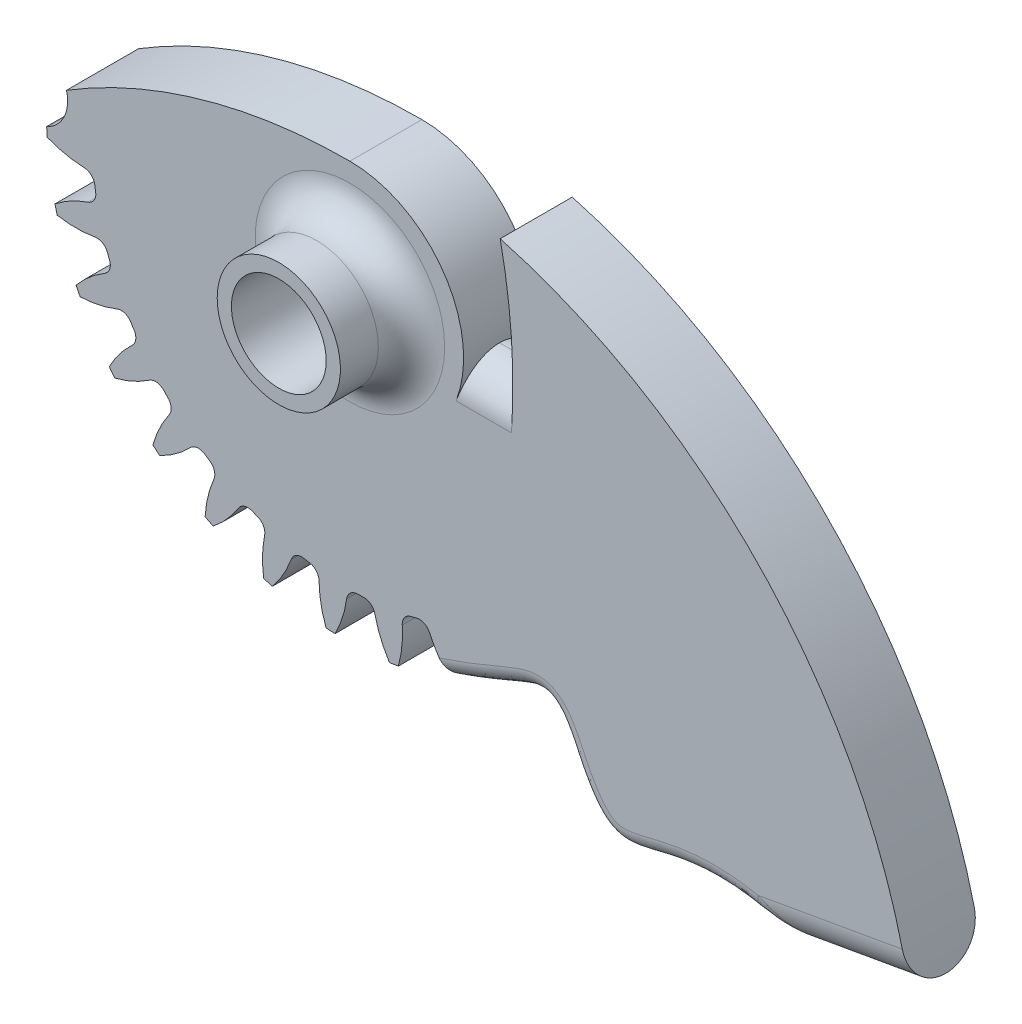
SolidWorks part; units mm, degrees
material "ABS"
ref_plane "Front" through (0, 0, 0) normal (0, 0, 1) x (1, 0, 0)
ref_plane "Top" through (0, 0, 0) normal (0, 1, 0) x (1, 0, 0)
ref_plane "Right" through (0, 0, 0) normal (1, 0, 0) x (0, 0, -1)
sketch "Sketch3" plane through (0, 0, 0) normal (0, 0, 1) x (1, 0, 0)
  circle A0 centre (0, 0) radius 40.64
  dimension "od" = 40.64
extrude "gearBody" add sketch "Sketch3" along normal blind 9.652
sketch "Sketch2" plane through (0, 0, 0) normal (0, 0, 1) x (1, 0, 0)
  line L0 (0, 0) -> (34.0786, 14.1158) construction
  line L1 (45.4751, -11.4855) -> (0, 0) construction
  line L2 (0, 0) -> (36.3143, 0) construction
  line L3 (38.0972, -0.458) -> (37.8451, -4.4001) construction
  line L5 (37.9712, -2.4291) -> (0, 0) construction
  line L7 (0, 0) -> (36.8864, 0) construction
  arc A0 (36.879, -0.7403) -> (36.6727, -3.9649) centre (0, 0) ccw construction
  arc A1 (40.637, 0.4947) -> (40.2427, -5.6687) centre (0, 0) ccw construction
  arc A2 (38.0972, -0.458) -> (37.8451, -4.4001) centre (0, 0) ccw construction
  arc A3 (34.9015, -2.6404) -> (34.9534, -1.8283) centre (0, 0) ccw construction
  arc A4 (45.4751, -11.4855) -> (35.6466, -3.6712) centre (32.0022, -18.3431) ccw construction
  arc A5 (45.4751, -11.4855) -> (46.5679, 5.5974) centre (0, 0) ccw construction
  arc A6 (46.5679, 5.5974) -> (35.8238, -0.9008) centre (34.0786, 14.1158) cw construction
  arc A7 (34.9534, -1.8283) -> (35.8238, -0.9008) centre (35.9376, -1.8798) cw construction
  arc A8 (35.6466, -3.6712) -> (34.9015, -2.6404) centre (35.8842, -2.7147) cw construction
  arc A9 (46.8801, 7.0756) -> (35.7652, -0.3962) centre (34.0786, 14.1158) cw
  arc A10 (34.4461, -1.8018) -> (35.7652, -0.3962) centre (35.9376, -1.8798) cw
  arc A11 (34.3949, -2.6021) -> (34.4461, -1.8018) centre (0, 0) ccw
  arc A12 (35.5241, -4.1642) -> (34.3949, -2.6021) centre (35.8842, -2.7147) cw
  arc A13 (45.5964, -12.9914) -> (35.5241, -4.1642) centre (32.0022, -18.3431) ccw
  arc A14 (45.5964, -12.9914) -> (46.8801, 7.0756) centre (0, 0) ccw
  point P6 (46.5679, 5.5974)
  point P22 (45.4751, -11.4855)
  dimension "D1" = 0.508
  dimension "baseDia" = 73.7729
  dimension "od" = 81.28
  dimension "pd" = 76.2
  dimension "rd" = 70.0024
  dimension "rFillet" = 0.9855
  dimension "pointX" = 46.5679
  dimension "pointY" = 5.5974
  dimension "CTT" = 3.9421
  dimension "flankCenterAngle" = 22.5
extrude "toothCut" cut sketch "Sketch2" along normal through all
pattern_circular "CirPattern1" count 30 over 360 about axis through (0, 0, 9.652) along (0, 0, -1) of "toothCut"
sketch "hub1Dia" plane through (0, 0, 0) normal (0, 0, -1) x (-1, 0, 0)
  circle A0 centre (0, 0) radius 12.7
  dimension "hub1Dia" = 25.4
sketch "hub2Dia" plane through (0, 0, 9.652) normal (0, 0, 1) x (1, 0, 0)
  circle A0 centre (0, 0) radius 12.7
  dimension "hub2dia" = 25.4
sketch "boreDia" plane through (0, 0, 0) normal (0, 0, 1) x (1, 0, 0)
  circle A0 centre (0, 0) radius 6.7469
  dimension "boreDia" = 13.4937
extrude "bore" cut sketch "boreDia" against normal mid plane 25400
sketch "Sketch4" plane through (0, 0, 9.652) normal (0, 0, 1) x (1, 0, 0)
  circle A0 centre (0, -57.15) radius 76.1746
  arc A2 (-41.7195, 6.5842) -> (41.7195, 6.5842) centre (0, 0) cw
  dimension "D1" = 152.3492
  dimension "D2" = 57.15
extrude "Cut-Extrude1" cut sketch "Sketch4" against normal through all contours A0 region at (0, 26.0638, 9.652)
sketch "Sketch5" plane through (0, 0, 9.652) normal (0, 0, 1) x (1, 0, 0)
  line L0 (0, 19.0246) -> (21.5163, 3.7176)
  line L1 (21.5163, 3.7176) -> (10.4433, -33.7781)
  line L2 (10.4433, -33.7781) -> (13.558, -38.3117)
  line L3 (0, 0) -> (0, -57.15) construction
  line L4 (0, -57.15) -> (-54.1615, -3.586) construction
  line L5 (0, -57.15) -> (65.9691, -95.2373) construction
  line L9 (0, -57.15) -> (75.0173, -43.9224) construction
  line L12 (60.232, -46.5295) -> (75.0173, -43.9224)
  line L13 (0, -57.15) -> (29.696, -40.005) construction
  line L14 (29.696, -40.005) -> (26.521, -34.5057) construction
  circle A1 centre (0, -57.15) radius 76.1746 construction
  arc A5 (0, 19.0246) -> (75.0173, -43.9224) centre (0, -57.15) cw
  circle A6 centre (0, -57.15) radius 21.59 construction
  arc A9 (10.6752, -34.1372) -> (8.9309, -33.317) centre (9.3176, -34.7596) ccw construction
  circle A12 centre (49.4934, -85.725) radius 40.64 construction
  spline S0 degree 3 poles (13.558, -38.3117) (21.087, -35.7646) (26.3659, -31.8249) (36.3578, -56.1686) (39.5345, -39.0169) (60.232, -46.5295) knots 0 0 0 0 0.118515 0.218515 1 1 1 1
  point P28 (21.569, -56.1981)
  dimension "D1" = 43.18
  dimension "D3" = 81.28
  dimension "D6" = 152.3492
  dimension "D2" = 120
  dimension "D4" = 57.15
  dimension "D8" = 57.15
  dimension "D7" = 60
  dimension "D9" = 34.29
  dimension "D10" = 6.35
  dimension "D5" = 80
extrude "Boss-Extrude1" add sketch "Sketch5" against normal up to surface (9.652 mm away) up to face at (6.7469, 0, 0)
sketch "Sketch6" plane through (0, 0, 9.652) normal (0, 0, 1) x (1, 0, 0)
  line L1 (-41.2993, 3.0747) -> (-42.3397, 6.1739)
  line L2 (15.875, 0) -> (21.209, 0)
  circle A0 centre (0, -57.15) radius 76.1746 construction
  arc A1 (75.0173, -43.9224) -> (-33.55, 11.2383) centre (0, -57.15) ccw construction
  circle A2 centre (0, 0) radius 15.875 construction
  arc A3 (0, 15.875) -> (15.875, 0) centre (0, 0) cw
  arc A4 (19.4523, 16.499) -> (-42.3397, 6.1739) centre (0, -57.15) ccw
  arc A5 (0, 15.875) -> (-41.2993, 3.0747) centre (0, -57.15) ccw
  circle A6 centre (0, 0) radius 21.209 construction
  circle A8 centre (-57.15, 0) radius 78.359 construction
  arc A9 (21.209, 0) -> (19.4523, 16.499) centre (-57.15, 0) ccw
  dimension "D4" = 57.15
  dimension "D1" = 31.75
  dimension "D2" = 42.418
  dimension "D3" = 156.718
extrude "Cut-Extrude2" cut sketch "Sketch6" against normal through all
sketch "Sketch7" plane through (0, 0, 9.652) normal (0, 0, 1) x (1, 0, 0)
  circle A0 centre (0, 0) radius 6.7469
  circle A1 centre (0, 0) radius 6.7469 construction
  circle A2 centre (0, 0) radius 8.255
  dimension "D1" = 16.51
extrude "spacer" add sketch "Sketch7" along normal blind 9.525
fillet "Fillet1" radius 4.445 1 edges at (8.255, 0, 9.652)
sketch "Sketch8" plane through (0, 0, 9.652) normal (0, 0, 1) x (1, 0, 0)
  line L0 (-38.1756, 5.1017) -> (-34.0224, 5.3247)
  line L1 (-34.0224, 5.3247) -> (-34.2899, 0.0545)
  line L2 (-34.2899, 0.0545) -> (-40.6263, -1.0555)
  arc A0 (-38.1756, 5.1017) -> (-40.6263, -1.0555) centre (-42.6187, 3.3039) cw
extrude "overextension stop" add sketch "Sketch8" against normal up to surface (9.652 mm away) up to face at (-13.508, -22.4485, 0)
sketch "Sketch11" plane through (0, 0, 9.652) normal (0, 0, 1) x (1, 0, 0)
  line L3 (15.2268, -0.635) -> (21.8414, -0.635)
  line L4 (15.2268, -0.635) -> (21.8414, -0.635)
  line L6 (-37.9725, 4.4812) -> (-39.287, 5.4618)
  line L7 (-39.287, 5.4618) -> (-10.5387, 26.6943)
  line L8 (-10.5387, 26.6943) -> (20.0731, 16.6327)
  arc A5 (-40.3928, -0.941) -> (-38.1756, 5.1017) centre (-42.6187, 3.3039) ccw construction
  arc A6 (15.2268, -0.635) -> (0, 15.24) centre (0, 0) ccw
  arc A7 (21.8414, -0.635) -> (20.0731, 16.6327) centre (-57.15, 0) ccw
  arc A8 (15.2268, -0.635) -> (0, 15.24) centre (0, 0) ccw
  arc A9 (21.8414, -0.635) -> (20.0731, 16.6327) centre (-57.15, 0) ccw
  arc A10 (0, 15.24) -> (-37.8436, 4.5604) centre (0, -57.15) ccw
  arc A11 (0, 15.24) -> (-37.9725, 4.4812) centre (0, -57.15) ccw
  dimension "D1" = 0.635
  dimension "D2" = 0.635
extrude "Cut-Extrude3" cut sketch "Sketch11" against normal through all
sketch "Sketch10" plane through (0, 0, 9.652) normal (0, 0, 1) x (1, 0, 0)
  circle A0 centre (0, 0) radius 6.35
  circle A1 centre (0, 0) radius 7.3025
  dimension "D1" = 12.7
  dimension "D2" = 14.605
extrude "bore dia" add sketch "Sketch10" along normal up to surface and the other way up to surface up to face at (8.255, 0, 19.177) other way up to face at (-12.6074, -23.7153, 0)
fillet "Fillet4" radius 4.826 4 edges at (18.5341, -0.635, 0) (18.5341, -0.635, 9.652) (67.6247, -45.2259, 0) (67.6247, -45.2259, 9.652)
fillet "Fillet3" radius 2.286 4 edges at (56.6479, -45.3986, 8.5331) (54.7143, -44.9405, 0.585)
equation "\"Bodytube_OD\"= 6.17in"
equation "\"Bodytube_ID\"= 5.998in"
equation "\"Fwd_Tube_Length\"= 40in"
equation "\"Mid_Tube_Length\"= 1in"
equation "\"Aft_Section_Length\"= 39in"
equation "\"Mid_Coupler_Length\"= 13in"
equation "\"Aft_Lower_Length\"= 22in"
equation "\"AB_Coupler_OD_Length\"= 1in"
equation "\"AB_Coupling_Section_Length\"= 0.375in"
equation "\"AB_Coupler_Length\"= \"AB_Coupler_OD_Length\" + \"AB_Coupling_Section_Length\" * 2"
equation "\"Cutout_Angle\"= 80"
equation "\"AB_Paddle_Height\"= 0.375in"
equation "\"AB_Coupler_Num_Screws\"= 4"
equation "\"Num_Cutouts\"= 3"
equation "\"AB_Coupler_OD\"= 6.17in"
equation "\"AB_Coupler_ID\"= 5.75in"
equation "\"AB_Coupler_Surface_Diameter\"= 5.998in"
equation "\"AB_Coupling_Screw_Diameter\"= 0.15748in"
equation "\"AB_Central_Bushing_Length\"= .4724in"
equation "\"Lead_Screw_Dist\"= 3.4in"
equation "\"Lead_Screw_Diam\"= 0.386in"
equation "\"Lead_Screw_Length\"= (\"Mid_Coupler_Length\" + 2*0.375in + 2*0.5in)"
equation "\"Paddle_Pin_Offset\"= .25in"
equation "\"Paddle_Pin_Radius\"= 2.25in"
equation "\"Fwd_BKHD_From_Top\"= 18in"
equation "\"D1@Sketch4\"=\"Bodytube_ID\""
equation "\"D2@Sketch4\"=\"Paddle_Pin_Radius\""
equation "\"D3@Sketch5\"=\"Paddle_Gear_OD\""
equation "\"D4@Sketch5\"=\"Paddle_Pin_Radius\""
equation "\"Motor_OD\"= 4in"
equation "\"Aft_Upper_Length\"= \"Aft_Section_Length\" - \"Aft_Lower_Length\" - \"AB_Coupler_OD_Length\""
equation "\"Paddle_Gear_OD\"= 3.2in"
equation "\"D5@Sketch5\"=\"Cutout_Angle\""
equation "\"D6@Sketch5\"=\"Bodytube_ID\""
equation "\"D1@Sketch6\"=\"AB_Coupler_ID\"-2*\"Paddle_Pin_Radius\""
equation "\"D2@Sketch6\"=\"Bodytube_OD\"-2*\"Paddle_Pin_Radius\""
equation "\"D3@Sketch6\"=\"Bodytube_OD\""
equation "\"D4@Sketch6\"=\"Paddle_Pin_Radius\""
equation "\"D8@Sketch5\"=\"Paddle_Pin_Radius\""
equation "\"Drive_Gear_OD\"= 1.7in"
equation "\"Fin_Thickness\"= .118in"
equation "\"Guiderail_Cutout_Diameter\"= 1.5in"
equation "\"DB9_Hole_Dist\"= 25mm"
equation "\"D1@Sketch5\"=\"Drive_Gear_OD\""
